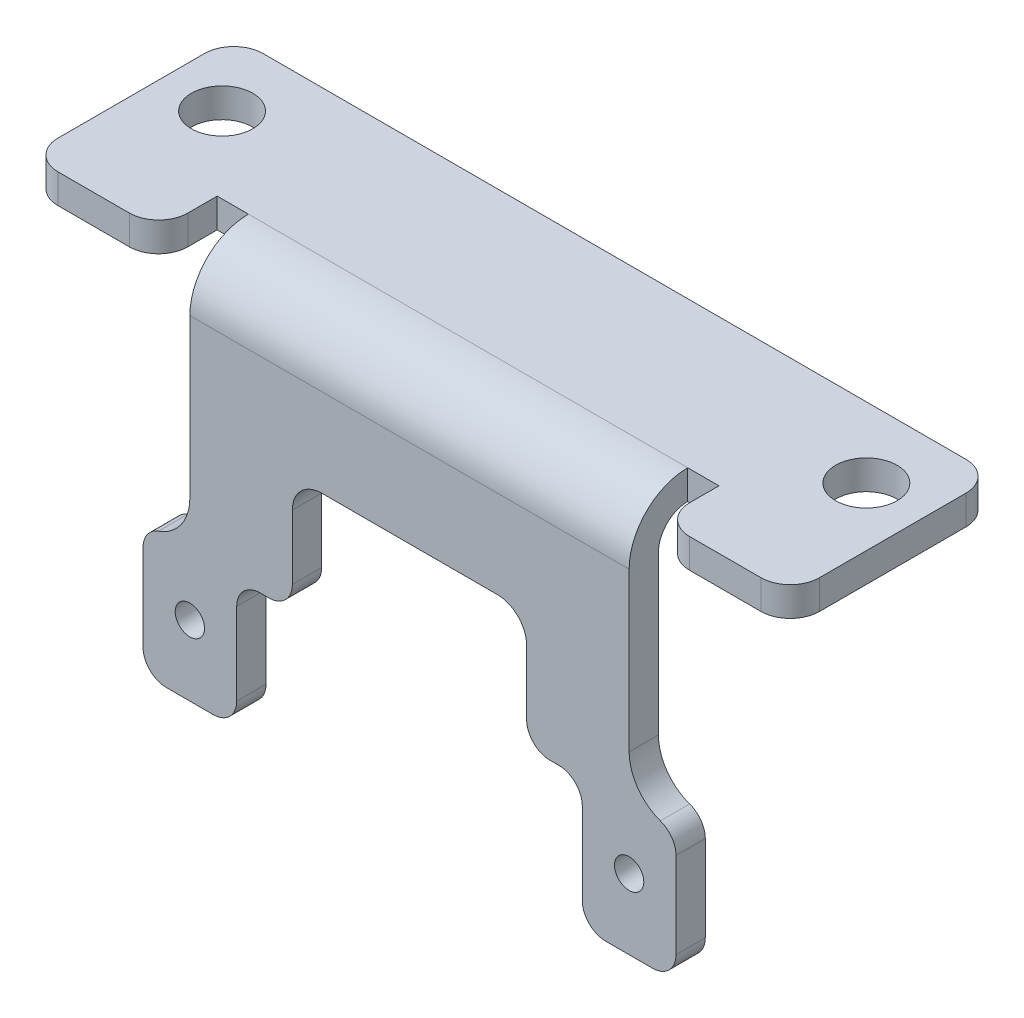
SolidWorks part; units mm, degrees
note: The reader was unsure of these and kept them because the rebuilt part matched: flange length of "Tôle pliée sur arête1".
material "1023 Tôle d'acier au carbone (SS)"
ref_plane "Plan de face" through (0, 0, 0) normal (0, 0, 1) x (1, 0, 0)
ref_plane "Plan de dessus" through (0, 0, 0) normal (0, 1, 0) x (1, 0, 0)
ref_plane "Plan de droite" through (0, 0, 0) normal (1, 0, 0) x (0, 0, -1)
sketch "Esquisse1" plane through (0, 0, 0) normal (0, 0, 1) x (1, 0, 0)
  line L0 (0, 50.5402) -> (0, 0) construction
  line L1 (-37.5, 0) -> (37.5, 0) construction
  line L2 (29.5, 6) -> (29.5, -8)
  line L3 (33.5, -12) -> (41.5, -12)
  line L4 (45.5, -8) -> (45.5, 6.6863)
  line L5 (45.5, 10) -> (37.5, 10) construction
  line L6 (37.5, 18) -> (37.5, 35)
  line L7 (47.5, 45) -> (65, 45)
  line L8 (65, 45) -> (65, 50)
  line L9 (65, 50) -> (-65, 50)
  line L10 (-45.5, 10) -> (-37.5, 10) construction
  line L11 (-15, 30) -> (15, 30)
  line L12 (20, 25) -> (20, 14)
  line L13 (24, 10) -> (25.5, 10)
  line L14 (-24, 10) -> (-25.5, 10)
  line L15 (-20, 25) -> (-20, 14)
  line L16 (-65, 45) -> (-65, 50)
  line L17 (-47.5, 45) -> (-65, 45)
  line L18 (-37.5, 18) -> (-37.5, 35)
  line L19 (-45.5, -8) -> (-45.5, 6.6863)
  line L20 (-33.5, -12) -> (-41.5, -12)
  line L21 (-29.5, 6) -> (-29.5, -8)
  circle A0 centre (37.5, 0) radius 2.5
  arc A1 (37.5, 18) -> (42.8333, 10.4575) centre (45.5, 18) ccw
  arc A2 (37.5, 35) -> (47.5, 45) centre (47.5, 35) cw
  arc A3 (41.5, -12) -> (45.5, -8) centre (41.5, -8) ccw
  arc A4 (29.5, -8) -> (33.5, -12) centre (33.5, -8) ccw
  arc A5 (15, 30) -> (20, 25) centre (15, 25) cw
  arc A6 (20, 14) -> (24, 10) centre (24, 14) ccw
  arc A7 (29.5, 6) -> (25.5, 10) centre (25.5, 6) ccw
  arc A8 (45.5, 6.6863) -> (42.8333, 10.4575) centre (41.5, 6.6863) ccw
  arc A11 (-45.5, 6.6863) -> (-42.8333, 10.4575) centre (-41.5, 6.6863) cw
  arc A12 (-29.5, 6) -> (-25.5, 10) centre (-25.5, 6) cw
  arc A13 (-20, 14) -> (-24, 10) centre (-24, 14) cw
  arc A14 (-15, 30) -> (-20, 25) centre (-15, 25) ccw
  arc A15 (-29.5, -8) -> (-33.5, -12) centre (-33.5, -8) cw
  arc A16 (-41.5, -12) -> (-45.5, -8) centre (-41.5, -8) cw
  arc A17 (-37.5, 35) -> (-47.5, 45) centre (-47.5, 35) ccw
  arc A18 (-37.5, 18) -> (-42.8333, 10.4575) centre (-45.5, 18) cw
  circle A19 centre (-37.5, 0) radius 2.5
  point P37 (65, 45)
  point P67 (0, 30)
  point P68 (0, 50)
  dimension "D1" = 5
  dimension "D4" = 10
  dimension "D12" = 10
  dimension "D13" = 4
  dimension "D14" = 4
  dimension "D15" = 5
  dimension "D16" = 4
  dimension "D17" = 4
  dimension "D18" = 4
  dimension "D2" = 75
  dimension "D3" = 12
  dimension "D5" = 8
  dimension "D6" = 8
  dimension "D7" = 50
  dimension "D8" = 65
  dimension "D9" = 5
  dimension "D10" = 30
  dimension "D11" = 40
sheet metal parameters "Tôlerie 1" thickness 5 parameters "D1"=5
base flange "Tôle de base pliée1" sketch "Esquisse1" thickness 5 reverse thickness direction yes parameters "D1"=5
edge flange "Tôle pliée sur arête1" sketch "Esquisse5" flange angle 90 flange length 30 flange position material outside bend radius 5 thickness 5 parameters "D6"=10
sketch "Esquisse5" plane through (0, 50, 0) normal (0, 1, 0) x (1, 0, 0)
  line L0 (65, 0) -> (-65, 0) construction
  line L1 (65, 0) -> (-65, 0)
  line L2 (-65, 0) -> (-65, 30)
  line L3 (-65, 30) -> (65, 30)
  line L4 (65, 30) -> (65, 0)
bend "Pli d'arête1" bend radius 5 bend angle 90 parameters "D5"=1
fillet "Congé1" radius 5 8 edges at (-65, 45, 2.5) (65, 45, 2.5) (-65, 48.5355, -1.4645) (65, 48.5355, -1.4645) (-65, 52.5, -30) (65, 52.5, -30)
sketch "Esquisse7" plane through (0, 55, 0) normal (0, 1, 0) x (1, 0, 0)
  line L0 (0, -5) -> (0, 30) construction
  line L1 (-47.5, -5) -> (47.5, -5) construction
  line L2 (60, 30) -> (-60, 30) construction
  line L3 (-64.1012, 18) -> (55, 18) construction
  circle A0 centre (55, 18) radius 5.25
  circle A1 centre (-55, 18) radius 5.25
  dimension "D1" = 110
  dimension "D2" = 10.5
  dimension "D3" = 12
extrude "Extrusion2" cut sketch "Esquisse7" against normal blind 10
sketch "Esquisse8" plane through (0, 0, 5) normal (0, 0, 1) x (1, 0, 0)
  line L0 (65, 55) -> (-65, 55) construction
  line L1 (37.5, 35) -> (65, 35)
  line L2 (37.5, 35) -> (37.5, 55)
  line L3 (37.5, 55) -> (65, 55)
  line L4 (65, 35) -> (65, 55)
  line L5 (-37.5, 35) -> (-65, 35)
  line L6 (-37.5, 35) -> (-37.5, 55)
  line L7 (-37.5, 55) -> (-65, 55)
  line L8 (-65, 35) -> (-65, 55)
  line L9 (-65, 50) -> (-65, 55) construction
extrude "Extrusion3" cut sketch "Esquisse8" against normal blind 10
sketch "Esquisse9" plane through (0, 55, 0) normal (0, 1, 0) x (1, 0, 0)
  line L1 (-65, 5) -> (-42.8333, 5)
  line L2 (-65, 5) -> (-65, 0)
  line L3 (-60, -5) -> (-47.8333, -5)
  line L4 (-42.8333, 5) -> (-42.8333, 0)
  line L5 (65, 5) -> (42.8333, 5)
  line L6 (65, 5) -> (65, 0)
  line L7 (60, -5) -> (47.8333, -5)
  line L8 (42.8333, 5) -> (42.8333, 0)
  arc A0 (-65, 0) -> (-60, -5) centre (-60, 0) ccw
  arc A1 (-47.8333, -5) -> (-42.8333, 0) centre (-47.8333, 0) ccw
  arc A2 (47.8333, -5) -> (42.8333, 0) centre (47.8333, 0) cw
  arc A3 (65, 0) -> (60, -5) centre (60, 0) cw
  point P16 (-42.8333, -5)
  point P19 (42.8333, -5)
  dimension "D1" = 5
base flange "Patte1" sketch "Esquisse9" thickness 5 reverse thickness direction yes parameters "D1"=5
flat pattern "Etat déplié1" [suppressed]
sketch "Lignes de pliage1" plane through (0, 0, 0) normal (0, 1, 0) x (-1, 0, 0)
bend of the flat pattern "Dépliage-<Pli d'arête1>1"
